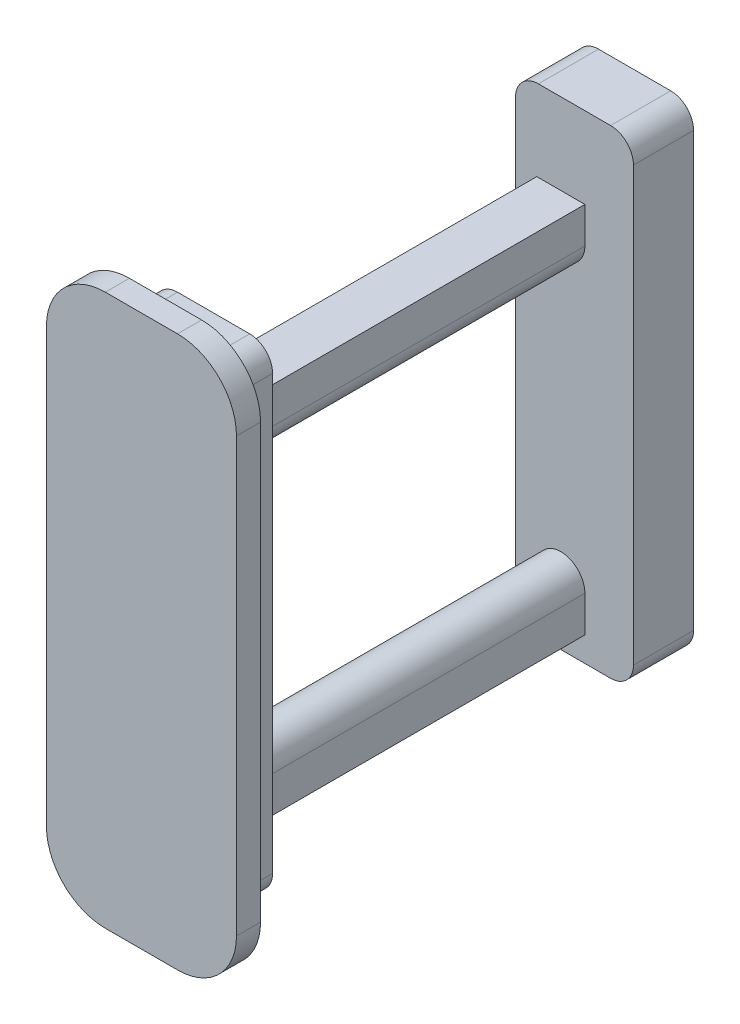
SolidWorks part; units mm, degrees
ref_plane "Front Plane" through (0, 0, 0) normal (0, 0, 1) x (1, 0, 0)
ref_plane "Top Plane" through (0, 0, 0) normal (0, 1, 0) x (1, 0, 0)
ref_plane "Right Plane" through (0, 0, 0) normal (1, 0, 0) x (0, 0, -1)
sketch "Sketch1" plane through (0, 0, 0) normal (0, 0, 1) x (1, 0, 0)
  line L0 (15.5302, -20) -> (21.5302, -20) construction
  line L1 (13.5302, 18) -> (13.5302, -18) construction
  line L2 (21.5302, 20) -> (15.5302, 20) construction
  line L3 (23.5302, -18) -> (23.5302, 18) construction
  line L4 (15.5302, -20) -> (21.5302, -20) construction
  line L5 (13.5302, 18) -> (13.5302, -18) construction
  line L6 (21.5302, 20) -> (15.5302, 20) construction
  line L7 (23.5302, -18) -> (23.5302, 18) construction
  line L8 (15.5302, -19.9) -> (21.5302, -19.9)
  line L9 (23.4302, -18) -> (23.4302, 18)
  line L10 (21.5302, 19.9) -> (15.5302, 19.9)
  line L11 (13.6302, 18) -> (13.6302, -18)
  arc A0 (21.5302, -20) -> (23.5302, -18) centre (21.5302, -18) ccw construction
  arc A1 (13.5302, -18) -> (15.5302, -20) centre (15.5302, -18) ccw construction
  arc A2 (15.5302, 20) -> (13.5302, 18) centre (15.5302, 18) ccw construction
  arc A3 (23.5302, 18) -> (21.5302, 20) centre (21.5302, 18) ccw construction
  arc A4 (21.5302, -20) -> (23.5302, -18) centre (21.5302, -18) ccw construction
  arc A5 (13.5302, -18) -> (15.5302, -20) centre (15.5302, -18) ccw construction
  arc A6 (15.5302, 20) -> (13.5302, 18) centre (15.5302, 18) ccw construction
  arc A7 (23.5302, 18) -> (21.5302, 20) centre (21.5302, 18) ccw construction
  arc A8 (21.5302, -19.9) -> (23.4302, -18) centre (21.5302, -18) ccw
  arc A9 (23.4302, 18) -> (21.5302, 19.9) centre (21.5302, 18) ccw
  arc A10 (15.5302, 19.9) -> (13.6302, 18) centre (15.5302, 18) ccw
  arc A11 (13.6302, -18) -> (15.5302, -19.9) centre (15.5302, -18) ccw
  dimension "D1" = 0.1
extrude "Boss-Extrude1" add sketch "Sketch1" against normal blind 4
sketch "Sketch2" plane through (0, 0, 0) normal (0, 0, 1) x (1, 0, 0)
  line L0 (0, 0) -> (25.8235, 0) construction
  line L1 (15.3952, 10.1523) -> (15.3952, 13.1523)
  line L2 (15.3952, 13.1523) -> (19.3952, 13.1523)
  line L3 (19.3952, 13.1523) -> (19.3952, 10.1523)
  line L7 (44.3952, -2.3477) -> (-14.3348, -2.3477) construction
  line L8 (19.3952, -17.8477) -> (19.3952, -14.8477)
  line L9 (15.3952, -17.8477) -> (19.3952, -17.8477)
  line L10 (15.3952, -14.8477) -> (15.3952, -17.8477)
  arc A0 (15.3952, 10.1523) -> (19.3952, 10.1523) centre (17.3952, 10.1523) ccw
  circle A1 centre (44.3952, -2.3477) radius 3.175 construction
  arc A3 (15.3952, -14.8477) -> (19.3952, -14.8477) centre (17.3952, -14.8477) cw
  dimension "D1" = 27
  dimension "D3" = 4
  dimension "D2" = 12.5
  dimension "D4" = 3
extrude "Boss-Extrude2" add sketch "Sketch2" against normal blind 30 from surface starting at face at (18.5302, 0, -4)
extrude "Boss-Extrude3" add sketch "Sketch1<2>" against normal blind 5 from surface starting at face at (17.3952, -15.8477, -34)
sketch "Sketch1<2>" plane through (0, 0, 0) normal (0, 0, 1) x (1, 0, 0) same geometry as "Sketch1"
chamfer "Chamfer1" distance 2 angle 45 8 edges at (19.3952, 11.6523, -4) (17.3952, 8.1523, -4) (17.3952, 13.1523, -4) (15.3952, 11.6523, -4) (19.3952, -16.3477, -4) (17.3952, -12.8477, -4) (15.3952, -16.3477, -4) (17.3952, -17.8477, -4)
sketch "Sketch3" plane through (0, 0, 0) normal (0, 0, 1) x (1, 0, 0)
  line L8 (15.5302, -22.9) -> (21.5302, -22.9)
  line L9 (26.4302, -18) -> (26.4302, 18)
  line L10 (21.5302, 22.9) -> (15.5302, 22.9)
  line L11 (10.6302, 18) -> (10.6302, -18)
  line L12 (15.5302, -22.9) -> (21.5302, -22.9)
  line L13 (26.4302, -18) -> (26.4302, 18)
  line L14 (21.5302, 22.9) -> (15.5302, 22.9)
  line L15 (10.6302, 18) -> (10.6302, -18)
  arc A8 (10.6302, -18) -> (15.5302, -22.9) centre (15.5302, -18) ccw
  arc A9 (21.5302, -22.9) -> (26.4302, -18) centre (21.5302, -18) ccw
  arc A10 (26.4302, 18) -> (21.5302, 22.9) centre (21.5302, 18) ccw
  arc A11 (15.5302, 22.9) -> (10.6302, 18) centre (15.5302, 18) ccw
  arc A12 (10.6302, -18) -> (15.5302, -22.9) centre (15.5302, -18) ccw
  arc A13 (21.5302, -22.9) -> (26.4302, -18) centre (21.5302, -18) ccw
  arc A14 (26.4302, 18) -> (21.5302, 22.9) centre (21.5302, 18) ccw
  arc A15 (15.5302, 22.9) -> (10.6302, 18) centre (15.5302, 18) ccw
  dimension "D1" = 3
extrude "Boss-Extrude4" add sketch "Sketch3" along normal blind 2
